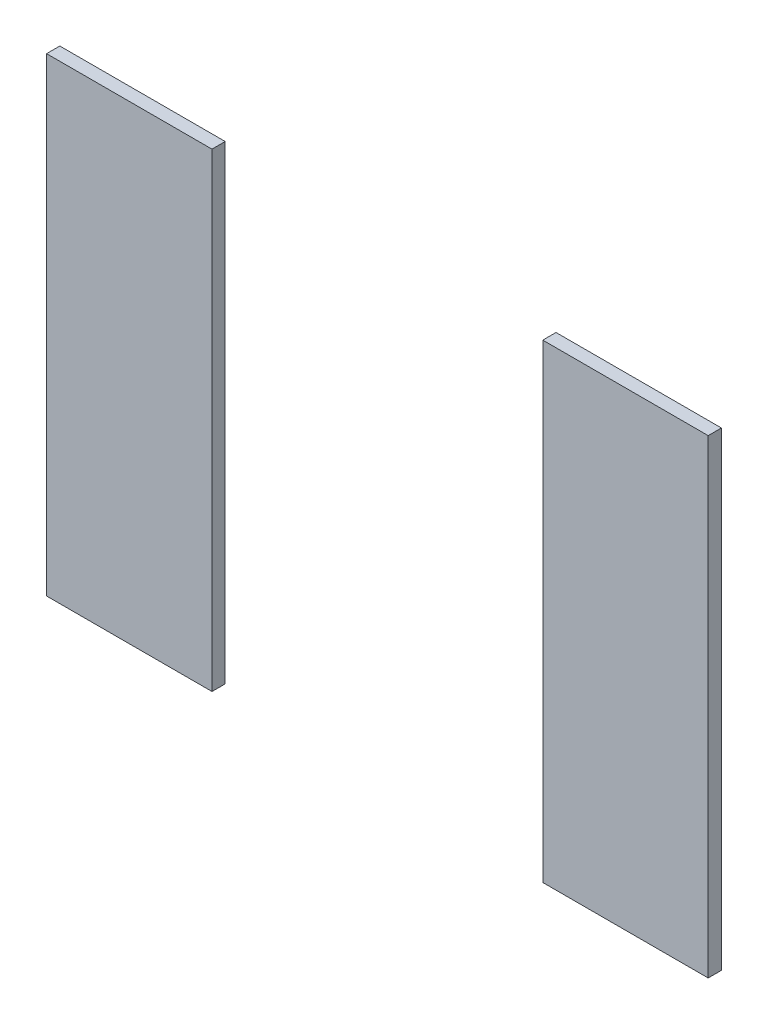
SolidWorks part; units mm, degrees
ref_plane "Front Plane" through (0, 0, 0) normal (0, 0, 1) x (1, 0, 0)
ref_plane "Top Plane" through (0, 0, 0) normal (0, 1, 0) x (1, 0, 0)
ref_plane "Right Plane" through (0, 0, 0) normal (1, 0, 0) x (0, 0, -1)
sketch "Sketch2" plane through (0, 0, 0) normal (0, 0, 1) x (1, 0, 0)
  line L0 (-500, 0) -> (500, 0)
  line L1 (-500, 0) -> (-500, -810)
  line L2 (500, 0) -> (500, -810)
  line L3 (-500, -810) -> (500, -810)
  line L4 (-250, 0) -> (-250, -810)
  line L5 (250, -810) -> (250, 0)
  line L6 (500, -243.561) -> (250, -243.561) construction
  line L7 (-500, -243.561) -> (-250, -243.561) construction
  line L8 (-500, -710) -> (500, -710)
  line L9 (340.1466, -710) -> (340.1466, -810) construction
  point P2 (0, 0)
  dimension "D1" = 250
  dimension "D2" = 810
  dimension "D3" = 1000
  dimension "D4" = 100
extrude "Boss-Extrude1" add sketch "Sketch2" along normal mid plane 20 contours L4 L0 L1 L3 | L5 L3 L2 L0 region at (-375, -355, 0) region at (375, -355, 0)
